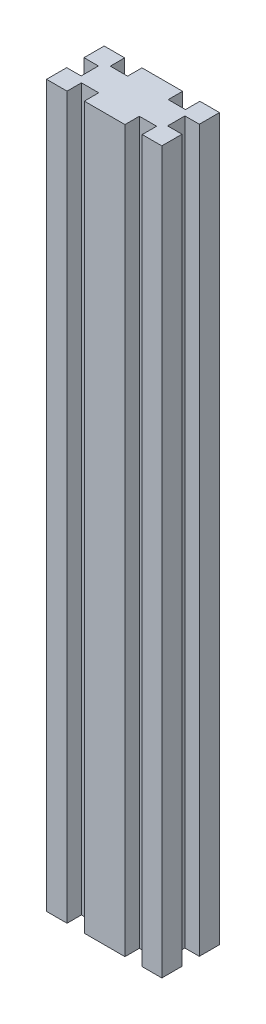
SolidWorks part; units mm, degrees
ref_plane "Спереди" through (0, 0, 0) normal (0, 0, 1) x (1, 0, 0)
ref_plane "Сверху" through (0, 0, 0) normal (0, 1, 0) x (1, 0, 0)
ref_plane "Справа" through (0, 0, 0) normal (1, 0, 0) x (0, 0, -1)
sketch "Эскиз1" plane through (0, 0, 0) normal (0, 1, 0) x (1, 0, 0)
  line L0 (5, 10) -> (35, 10) construction
  line L1 (0, 0) -> (7.1145, 0)
  line L2 (0, 20) -> (0, 13)
  line L3 (0, 20) -> (7.1145, 20)
  line L4 (40, 20) -> (40, 13)
  line L5 (30.2024, 15) -> (30.2024, 5) construction
  line L6 (10.1145, 15) -> (10.1145, 5) construction
  line L7 (20, 20) -> (20, 0) construction
  line L8 (7.1145, 20) -> (7.1145, 15)
  line L9 (7.1145, 15) -> (13.1145, 15)
  line L10 (13.1145, 15) -> (13.1145, 20)
  line L11 (13.1145, 20) -> (27.2024, 20)
  line L12 (27.2024, 20) -> (27.2024, 15)
  line L13 (27.2024, 15) -> (33.2024, 15)
  line L14 (33.2024, 15) -> (33.2024, 20)
  line L15 (33.2024, 20) -> (40, 20)
  line L16 (7.1145, 0) -> (7.1145, 5)
  line L17 (7.1145, 5) -> (13.1145, 5)
  line L18 (13.1145, 5) -> (13.1145, 0)
  line L19 (13.1145, 0) -> (27.2024, 0)
  line L20 (27.2024, 0) -> (27.2024, 5)
  line L21 (27.2024, 5) -> (33.2024, 5)
  line L22 (33.2024, 5) -> (33.2024, 0)
  line L23 (33.2024, 0) -> (40, 0)
  line L24 (40, 13) -> (35, 13)
  line L25 (35, 13) -> (35, 7)
  line L26 (35, 7) -> (40, 7)
  line L27 (40, 7) -> (40, 0)
  line L28 (0, 13) -> (5, 13)
  line L29 (5, 13) -> (5, 7)
  line L30 (5, 7) -> (0, 7)
  line L31 (0, 7) -> (0, 0)
  point P35 (0, 10.45)
  point P38 (39.9443, 10.45)
  point P39 (0, 0)
  point P40 (42.8896, 9.8459)
  point P41 (0, 0)
  point P42 (37.0746, 9.3928)
  point P43 (30, 4.4841)
  point P44 (30.2024, 15.2077)
  point P45 (10, 4.4841)
  point P46 (10.1145, 15.2077)
  point P47 (5, 9.3928)
  dimension "D1" = 6
  dimension "D2" = 6
  dimension "D3" = 6
  dimension "D4" = 6
  dimension "D5" = 5
  dimension "D6" = 6
  dimension "D7" = 6
  dimension "D8" = 40
  dimension "D9" = 20
  dimension "D10" = 5
extrude "Бобышка-Вытянуть1" add sketch "Эскиз1" along normal blind 250
